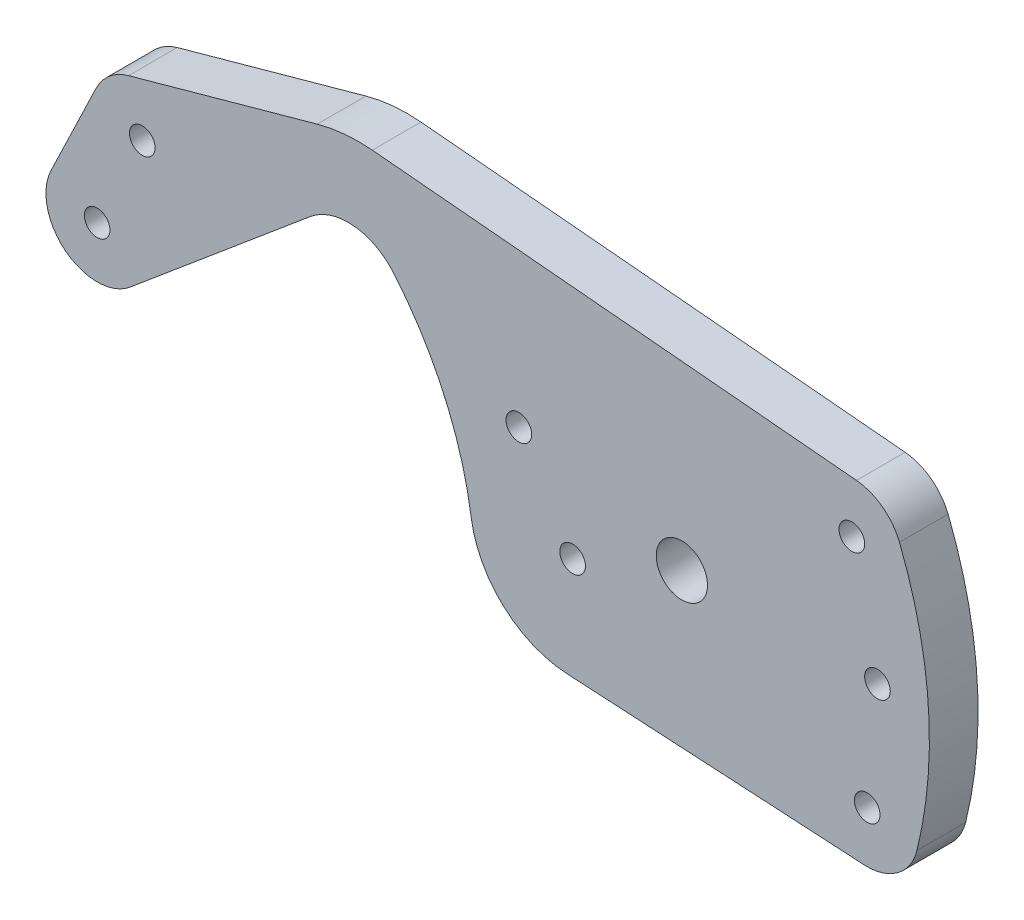
SolidWorks part; units mm, degrees
ref_plane "Front Plane" through (0, 0, 0) normal (0, 0, 1) x (1, 0, 0)
ref_plane "Top Plane" through (0, 0, 0) normal (0, 1, 0) x (1, 0, 0)
ref_plane "Right Plane" through (0, 0, 0) normal (1, 0, 0) x (0, 0, -1)
sketch "Sketch1" plane through (0, 0, 0) normal (0, 0, 1) x (1, 0, 0)
  line L1 (-5, -5) -> (5, -5) construction
  line L2 (-5, -5) -> (-5, 5) construction
  line L3 (-5, 5) -> (5, 5) construction
  line L4 (5, -5) -> (5, 5) construction
  line L5 (-5, -5) -> (5, 5) construction
  line L6 (-5, 5) -> (5, -5) construction
  line L7 (35.613, -31.9838) -> (-22.4565, -28.6732)
  line L9 (-114.3299, 24.3337) -> (-123.1299, 6.0337)
  line L10 (-107.6899, -5.9604) -> (-72.4818, 23.5827)
  line L11 (-107.9907, 29.6362) -> (-71.1481, 39.8558)
  line L13 (-60.4213, 40.8249) -> (34.0849, 32.2592)
  line L15 (-65.6167, 45.8212) -> (-65.8285, 40.8257) construction
  line L16 (-65.0895, 14.7729) -> (-108.3178, -21.5) construction
  line L17 (50.9822, -33.5) -> (-177.2181, -33.5) construction
  line L19 (-151.9038, 49.4802) -> (40.5772, 41.3179) construction
  circle A0 centre (0, 0) radius 5
  circle A1 centre (-31.8178, 8.3) radius 2.5
  circle A2 centre (-21.3178, -8.7) radius 2.5
  circle A3 centre (33.1822, 22.3) radius 2.5
  circle A4 centre (38.1822, -0.1) radius 2.5
  circle A5 centre (36.1822, -22) radius 2.5
  circle A6 centre (36.1822, -22) radius 2.5 construction
  circle A7 centre (38.1822, -0.1) radius 2.5 construction
  circle A8 centre (33.1822, 22.3) radius 2.5 construction
  circle A9 centre (-31.8178, 8.3) radius 2.5 construction
  circle A10 centre (-21.3178, -8.7) radius 2.5 construction
  arc A12 (-41.1103, -11.612) -> (-22.4565, -28.6732) centre (-21.3178, -8.7) ccw
  arc A13 (32.9852, -31.834) -> (27.9855, 32.812) centre (-34.3029, -4.5217) ccw construction
  arc A14 (45.8883, -24.4068) -> (42.4751, 25.9934) centre (-34.3029, -4.5217) ccw
  arc A15 (35.613, -31.9838) -> (45.8883, -24.4068) centre (36.1822, -22) ccw
  arc A16 (42.4751, 25.9934) -> (34.0849, 32.2592) centre (33.1822, 22.3) ccw
  circle A17 centre (-105.3178, 20) radius 2.5
  circle A18 centre (-34.3029, -4.5217) radius 82.6199 construction
  circle A19 centre (-114.1178, 1.7) radius 2.5
  circle A21 centre (-105.3178, 20) radius 2.5 construction
  circle A22 centre (-114.1178, 1.7) radius 2.5 construction
  arc A23 (-107.9907, 29.6362) -> (-114.3299, 24.3337) centre (-105.3178, 20) ccw
  arc A24 (-123.1299, 6.0337) -> (-107.6899, -5.9604) centre (-114.1178, 1.7) ccw
  arc A27 (-60.4213, 40.8249) -> (-71.1481, 39.8558) centre (-63.1293, 10.9473) ccw
  circle A31 centre (-34.3029, -4.5217) radius 72.6199 construction
  arc A32 (-41.1103, -11.612) -> (-56.2797, 22.1652) centre (-108.3178, -21.5) ccw
  arc A33 (-32.9664, -24.9645) -> (-65.8285, 40.8257) centre (-108.3178, -21.5) ccw construction
  circle A34 centre (0, 0) radius 35 construction
  arc A35 (-56.2797, 22.1652) -> (-72.4818, 23.5827) centre (-65.0895, 14.7729) ccw
  circle A36 centre (-65.0895, 14.7729) radius 10.5004 construction
  circle A37 centre (-108.3178, -21.5) radius 67.9309 construction
  circle A38 centre (-108.3178, -21.5) radius 75.4309 construction
  circle A39 centre (-108.3178, -21.5) radius 10.5004 construction
  circle A40 centre (-108.3178, -21.5) radius 11.5004 construction
  point P35 (50.3427, -4.5217)
  point P36 (-64.6705, 41.7981)
  point P37 (37.1696, 16.7103)
  point P54 (-36.0565, -0.0269)
  point P70 (0, 0)
  point P75 (-40.8381, -1.4887)
  dimension "D1" = 10
  dimension "D3" = 7.5
  dimension "D5" = 5
  dimension "D7" = 40
  dimension "D4" = 30
  dimension "D2" = 10
  dimension "D8" = 1
extrude "Boss-Extrude1" add sketch "Sketch1" along normal blind 9.5 contours A0 L4 L3 | A0 L1 L4 | A0 L2 L1 | A0 L3 L2 region at (-20.6603, 7.4815, 0)
